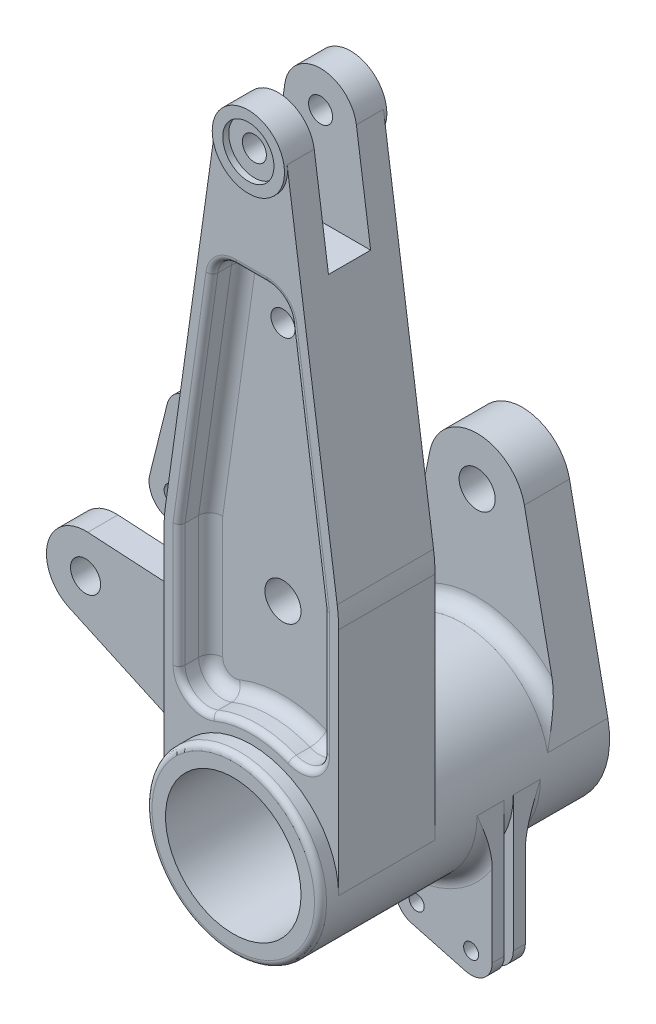
SolidWorks part; units mm, degrees
ref_plane "Front Plane" through (0, 0, 0) normal (0, 0, 1) x (1, 0, 0)
ref_plane "Top Plane" through (0, 0, 0) normal (0, 1, 0) x (1, 0, 0)
ref_plane "Right Plane" through (0, 0, 0) normal (1, 0, 0) x (0, 0, -1)
sketch "Sketch1" plane through (0, 0, 0) normal (0, 0, 1) x (1, 0, 0)
  circle A0 centre (0, 0) radius 22.5
  circle A1 centre (0, 0) radius 29
  dimension "D1" = 45
  dimension "D2" = 6.5
extrude "Boss-Extrude1" add sketch "Sketch1" along normal blind 96
sketch "Sketch2" plane through (0, 0, 0) normal (0, 0, -1) x (-1, 0, 0)
  line L0 (0, 0) -> (0, 65) construction
  line L1 (-28.4141, 5.8) -> (-15.6767, 68.2)
  line L2 (15.6769, 68.1992) -> (22.86, 33)
  line L3 (22.86, 33) -> (101.2121, 44.9958)
  line L4 (101.2121, 44.9958) -> (110.5, 7.633)
  line L5 (110.5, 7.633) -> (9.5035, -27.3986)
  line L6 (0, 0) -> (105.856, 26.3144) construction
  arc A0 (-15.6767, 68.2) -> (15.6769, 68.1992) centre (0, 65) cw
  circle A1 centre (0, 0) radius 29
  circle A2 centre (0, 0) radius 29
  circle M7 centre (0, 0) radius 29
  dimension "D2" = 16
  dimension "D1" = 0
  dimension "D3" = 65
  dimension "D4" = 33
  dimension "D5" = 110.5
  dimension "D6" = 38.5
  dimension "D7" = 76.04
  dimension "D8" = 22.86
extrude "Boss-Extrude2" add sketch "Sketch2" against normal blind 15 contours A0 L1 L5 L4 L3 L2 M7 region at (-41.2413, 26.7949, 0)
fillet "Fillet1" radius 8 2 edges at (-101.2121, 44.9958, 7.5) (-110.5, 7.633, 7.5)
fillet "Fillet2" radius 20 1 edges at (-22.86, 33, 7.5)
sketch "Sketch3" plane through (0, 0, 15) normal (0, 0, 1) x (1, 0, 0)
  line L0 (-105.8547, 26.3197) -> (-62.2845, 15.4888) construction
  line L2 (-58.6658, 30.0457) -> (-65.9031, 0.9318) construction
  line L5 (-15.6769, 68.1992) -> (-19.0538, 51.6515)
  line L6 (-41.6767, 35.8809) -> (-93.9982, 43.8914)
  line L7 (-102.9727, 37.9135) -> (-108.7368, 14.726)
  line L8 (-103.5947, 5.2378) -> (-9.5035, -27.3986)
  line L9 (28.4141, 5.8) -> (15.6767, 68.2)
  line L10 (-15.6769, 68.1992) -> (-19.0538, 51.6515)
  line L11 (-41.6767, 35.8809) -> (-93.9982, 43.8914)
  line L12 (-102.9727, 37.9135) -> (-108.7368, 14.726)
  line L13 (-103.5947, 5.2378) -> (-9.5035, -27.3986)
  line L14 (28.4141, 5.8) -> (15.6767, 68.2)
  circle A0 centre (-95.209, 35.9835) radius 3
  circle A1 centre (-100.9731, 12.796) radius 3
  circle A2 centre (0, 65) radius 6
  circle A3 centre (-58.6658, 30.0457) radius 3
  circle A4 centre (-65.9031, 0.9318) radius 3
  arc A5 (-41.6767, 35.8809) -> (-19.0538, 51.6515) centre (-38.6499, 55.6505) ccw
  arc A6 (-93.9982, 43.8914) -> (-102.9727, 37.9135) centre (-95.209, 35.9835) ccw
  arc A7 (-108.7368, 14.726) -> (-103.5947, 5.2378) centre (-100.9731, 12.796) ccw
  arc A8 (28.4141, 5.8) -> (-9.5035, -27.3986) centre (0, 0) ccw
  arc A9 (15.6767, 68.2) -> (-15.6769, 68.1992) centre (0, 65) ccw
  arc A10 (-41.6767, 35.8809) -> (-19.0538, 51.6515) centre (-38.6499, 55.6505) ccw
  arc A11 (-93.9982, 43.8914) -> (-102.9727, 37.9135) centre (-95.209, 35.9835) ccw
  arc A12 (-108.7368, 14.726) -> (-103.5947, 5.2378) centre (-100.9731, 12.796) ccw
  arc A13 (28.4141, 5.8) -> (-9.5035, -27.3986) centre (0, 0) ccw
  arc A14 (15.6767, 68.2) -> (-15.6769, 68.1992) centre (0, 65) ccw
  circle A15 centre (-84.0696, 20.9042) radius 5
  point P23 (-62.2845, 15.4888)
  dimension "D2" = 10
  dimension "D3" = 6
  dimension "D4" = 12
  dimension "D5" = 30
  dimension "D6" = 45
  dimension "D1" = 0
extrude "Cut-Extrude1" cut sketch "Sketch3" against normal blind 15 contours A0 | A1 | A3 | A4 | A2 | A15
sketch "Sketch7" plane through (0, 0, 15) normal (0, 0, 1) x (1, 0, 0)
  line L0 (-41.6767, 35.8809) -> (-53.6045, -12.1018)
  line L3 (-65.9031, 0.9318) -> (-100.9731, 12.796) construction
  line L5 (-15.6769, 68.1992) -> (-19.0538, 51.6515)
  line L6 (-41.6767, 35.8809) -> (-93.9982, 43.8914)
  line L7 (-102.9727, 37.9135) -> (-108.7368, 14.726)
  line L8 (-103.5947, 5.2378) -> (-9.5035, -27.3986)
  line L9 (28.4141, 5.8) -> (15.6767, 68.2)
  line L10 (-15.6769, 68.1992) -> (-19.0538, 51.6515)
  line L11 (-41.6767, 35.8809) -> (-93.9982, 43.8914)
  line L12 (-102.9727, 37.9135) -> (-108.7368, 14.726)
  line L13 (-103.5947, 5.2378) -> (-9.5035, -27.3986)
  line L14 (28.4141, 5.8) -> (15.6767, 68.2)
  arc A5 (-41.6767, 35.8809) -> (-19.0538, 51.6515) centre (-38.6499, 55.6505) ccw
  arc A6 (-93.9982, 43.8914) -> (-102.9727, 37.9135) centre (-95.209, 35.9835) ccw
  arc A7 (-108.7368, 14.726) -> (-103.5947, 5.2378) centre (-100.9731, 12.796) ccw
  arc A8 (28.4141, 5.8) -> (-9.5035, -27.3986) centre (0, 0) ccw
  arc A9 (15.6767, 68.2) -> (-15.6769, 68.1992) centre (0, 65) ccw
  arc A10 (-41.6767, 35.8809) -> (-19.0538, 51.6515) centre (-38.6499, 55.6505) ccw
  arc A11 (-93.9982, 43.8914) -> (-102.9727, 37.9135) centre (-95.209, 35.9835) ccw
  arc A12 (-108.7368, 14.726) -> (-103.5947, 5.2378) centre (-100.9731, 12.796) ccw
  arc A13 (28.4141, 5.8) -> (-9.5035, -27.3986) centre (0, 0) ccw
  arc A14 (15.6767, 68.2) -> (-15.6769, 68.1992) centre (0, 65) ccw
  circle M13 centre (-100.9731, 12.796) radius 3
  circle M14 centre (-58.6658, 30.0457) radius 3
  circle M15 centre (-65.9031, 0.9318) radius 3
  circle M17 centre (-95.209, 35.9835) radius 3
  line M20 (-41.6767, 35.8809) -> (-93.9982, 43.8914)
  arc M21 (-93.9982, 43.8914) -> (-102.9727, 37.9135) centre (-95.209, 35.9835) ccw
  line M22 (-102.9727, 37.9135) -> (-108.7368, 14.726)
  arc M23 (-108.7368, 14.726) -> (-103.5947, 5.2378) centre (-100.9731, 12.796) ccw
  line M24 (-103.5947, 5.2378) -> (-9.5035, -27.3986)
  dimension "D1" = 0
extrude "Cut-Extrude3" cut sketch "Sketch7" against normal mid plane 5 from offset 7.5 contours L0 M20 M21 M22 M23 M24 M14 M17 M15 M13 region at (-75.0763, 18.6886, 15) offset against normal yes
ref_plane "Plane1" through (0, 0, 74) normal (0, 0, 1) x (1, 0, 0)
sketch "Sketch8" plane through (0, 0, 74) normal (0, 0, 1) x (1, 0, 0)
  line L0 (-29, 0) -> (-29, 80)
  line L1 (-29, 80) -> (-11.883, 201.6717)
  line L2 (11.883, 201.6717) -> (29, 80)
  line L3 (29, 80) -> (29, 0)
  line L4 (0, 0) -> (0, 200) construction
  line L5 (0, 0) -> (0, 200) construction
  circle A0 centre (0, 0) radius 29 construction
  circle A1 centre (0, 0) radius 29
  arc A2 (-11.883, 201.6717) -> (11.883, 201.6717) centre (0, 200) cw
  circle A3 centre (0, 200) radius 12
  circle A4 centre (0, 200) radius 4
  circle A5 centre (0, 200) radius 8.5
  dimension "D3" = 12
  dimension "D4" = 8
  dimension "D5" = 17
  dimension "D1" = 200
  dimension "D2" = 80
extrude "Boss-Extrude3" add sketch "Sketch8" along normal mid plane 32 contours A3 L1 L0 A1 L3 L2 | A2 A3 A5 | A5 A4 | A4 region at (0, 96.6166, 74) region at (0, 211.6606, 74) region at (0, 200, 74) region at (-8.2596, 200, 74)
sketch "Sketch9" plane through (0, 0, 90) normal (0, 0, 1) x (1, 0, 0)
  line L0 (-12.1335, 164) -> (-24, 79.65)
  line L1 (-24, 79.65) -> (-24, 24.0832)
  line L2 (24, 24.0832) -> (24, 79.65)
  line L3 (24, 79.65) -> (12.1335, 164)
  line L4 (29, 80) -> (11.883, 201.6717)
  line L5 (-11.883, 201.6717) -> (-29, 80)
  line L6 (-29, 80) -> (-29, 0)
  line L7 (29, 0) -> (29, 80)
  line L8 (29, 80) -> (11.883, 201.6717)
  line L9 (-11.883, 201.6717) -> (-29, 80)
  line L10 (-29, 80) -> (-29, 0)
  line L11 (29, 0) -> (29, 80)
  line L12 (-12.1335, 164) -> (12.1335, 164)
  line L13 (24, 79.65) -> (6.9317, 200.9752) construction
  line L14 (-6.9317, 200.9752) -> (-24, 79.65) construction
  arc A2 (11.883, 201.6717) -> (-11.883, 201.6717) centre (0, 200) ccw
  arc A3 (29, 0) -> (-29, 0) centre (0, 0) ccw
  arc A4 (11.883, 201.6717) -> (-11.883, 201.6717) centre (0, 200) ccw
  arc A5 (29, 0) -> (-29, 0) centre (0, 0) ccw
  arc A7 (24, 24.0832) -> (-24, 24.0832) centre (0, 0) ccw
  arc A9 (6.9317, 200.9752) -> (-6.9317, 200.9752) centre (0, 200) ccw construction
  dimension "D5" = 36
  dimension "D1" = 0
  dimension "D4" = 5
extrude "Cut-Extrude4" cut sketch "Sketch9" against normal blind 10.5 contours A7 L2 L3 L12 L0 L1 region at (0, 90.281, 90)
fillet "Fillet3" radius 8 4 edges at (-24, 24.0832, 84.75) (24, 24.0832, 84.75) (-12.1335, 164, 84.75) (12.1335, 164, 84.75)
fillet "Fillet4" radius 50 2 edges at (29, 80, 74) (-29, 80, 74)
fillet "Fillet5" radius 4 10 edges at (-20.4508, 32.1854, 79.5) (0, 34, 79.5) (20.4508, 32.1854, 79.5) (24, 59.2415, 79.5) (-24, 59.2415, 79.5) (18.5511, 118.3822, 79.5) (10.4282, 162.038, 79.5) (-18.5511, 118.3822, 79.5) (-10.4282, 162.038, 79.5) (0, 164, 79.5)
sketch "Sketch10" plane through (0, 0, 58) normal (0, 0, -1) x (-1, 0, 0)
  line L0 (-12.1335, 164) -> (-23.8101, 81)
  line L3 (23.5612, 82.7691) -> (12.1335, 164)
  line L4 (-11.883, 201.6717) -> (-28.5124, 83.4657)
  line L5 (-29, 76.5002) -> (-29, 0)
  line L6 (29, 0) -> (29, 76.5002)
  line L7 (28.5124, 83.4657) -> (11.883, 201.6717)
  line L8 (-11.883, 201.6717) -> (-28.5124, 83.4657)
  line L9 (-29, 76.5002) -> (-29, 0)
  line L10 (29, 0) -> (29, 76.5002)
  line L11 (28.5124, 83.4657) -> (11.883, 201.6717)
  line L13 (-12.1335, 164) -> (12.1335, 164)
  line L14 (-23.8101, 81) -> (23.7745, 81)
  line L15 (-24, 76.5002) -> (-24, 24.0832) construction
  line L16 (24, 24.0832) -> (24, 76.5002) construction
  line L18 (-6.9317, 200.9752) -> (-23.5612, 82.7691) construction
  line L19 (23.5612, 82.7691) -> (6.9317, 200.9752) construction
  arc A2 (23.7745, 81) -> (23.5612, 82.7691) centre (-21, 76.5002) ccw
  arc A4 (-28.5124, 83.4657) -> (-29, 76.5002) centre (21, 76.5002) ccw
  arc A5 (29, 0) -> (-29, 0) centre (0, 0) ccw
  arc A6 (29, 76.5002) -> (28.5124, 83.4657) centre (-21, 76.5002) ccw
  arc A7 (11.883, 201.6717) -> (-11.883, 201.6717) centre (0, 200) ccw
  arc A8 (-28.5124, 83.4657) -> (-29, 76.5002) centre (21, 76.5002) ccw
  arc A9 (29, 0) -> (-29, 0) centre (0, 0) ccw
  arc A10 (29, 76.5002) -> (28.5124, 83.4657) centre (-21, 76.5002) ccw
  arc A11 (11.883, 201.6717) -> (-11.883, 201.6717) centre (0, 200) ccw
  arc A12 (24, 24.0832) -> (-24, 24.0832) centre (0, 0) ccw construction
  arc A13 (-23.5612, 82.7691) -> (-24, 76.5002) centre (21, 76.5002) ccw construction
  arc A15 (24, 76.5002) -> (23.5612, 82.7691) centre (-21, 76.5002) ccw construction
  arc A16 (6.9317, 200.9752) -> (-6.9317, 200.9752) centre (0, 200) ccw construction
  point P28 (0, 29)
  dimension "D4" = 52
  dimension "D3" = 36
  dimension "D1" = 0
  dimension "D2" = 5
extrude "Cut-Extrude5" cut sketch "Sketch10" against normal blind 10.5 contours L3 L13 L0 L14 A2
fillet "Fillet6" radius 8 4 edges at (-23.7745, 81, 63.25) (-12.1335, 164, 63.25) (12.1335, 164, 63.25) (23.8101, 81, 63.25)
fillet "Fillet7" radius 4 8 edges at (-20.6439, 83.7519, 68.5) (-17.815, 123.6145, 68.5) (-10.4282, 162.038, 68.5) (0, 81, 68.5) (20.6439, 83.7519, 68.5) (17.815, 123.6145, 68.5) (10.4282, 162.038, 68.5) (0, 164, 68.5)
sketch "Sketch13" plane through (0, 0, 74) normal (0, 0, 1) x (1, 0, 0)
  line L0 (-16.62, 168) -> (16.62, 168)
  line L4 (29, 0) -> (29, 76.5002)
  line L5 (28.5124, 83.4657) -> (11.883, 201.6717)
  line L6 (-11.883, 201.6717) -> (-28.5124, 83.4657)
  line L7 (-29, 76.5002) -> (-29, 0)
  line L8 (29, 0) -> (29, 76.5002)
  line L9 (16.62, 168) -> (11.883, 201.6717)
  line L10 (-11.883, 201.6717) -> (-16.62, 168)
  line L11 (-29, 76.5002) -> (-29, 0)
  arc A4 (29, 76.5002) -> (28.5124, 83.4657) centre (-21, 76.5002) ccw
  arc A5 (11.883, 201.6717) -> (-11.883, 201.6717) centre (0, 200) ccw
  arc A6 (-28.5124, 83.4657) -> (-29, 76.5002) centre (21, 76.5002) ccw
  arc A7 (29, 0) -> (-29, 0) centre (0, 0) ccw
  arc A8 (29, 76.5002) -> (28.5124, 83.4657) centre (-21, 76.5002) ccw
  arc A9 (11.883, 201.6717) -> (-11.883, 201.6717) centre (0, 200) ccw
  arc A10 (-28.5124, 83.4657) -> (-29, 76.5002) centre (21, 76.5002) ccw
  arc A11 (29, 0) -> (-29, 0) centre (0, 0) ccw
  dimension "D2" = 32
  dimension "D1" = 0
extrude "Cut-Extrude7" cut sketch "Sketch13" against normal mid plane 14 contours L9 A9 L10 L0
sketch "Sketch11" plane through (0, 0, 58) normal (0, 0, -1) x (-1, 0, 0)
  line L4 (-11.883, 201.6717) -> (-28.5124, 83.4657)
  line L5 (-29, 76.5002) -> (-29, 0)
  line L6 (29, 0) -> (29, 76.5002)
  line L7 (28.5124, 83.4657) -> (11.883, 201.6717)
  line L8 (-11.883, 201.6717) -> (-28.5124, 83.4657)
  line L9 (-29, 76.5002) -> (-29, 0)
  line L10 (29, 0) -> (29, 76.5002)
  line L11 (28.5124, 83.4657) -> (11.883, 201.6717)
  circle A0 centre (0, 200) radius 12
  arc A4 (-28.5124, 83.4657) -> (-29, 76.5002) centre (21, 76.5002) ccw
  arc A5 (29, 0) -> (-29, 0) centre (0, 0) ccw
  arc A6 (29, 76.5002) -> (28.5124, 83.4657) centre (-21, 76.5002) ccw
  arc A7 (11.883, 201.6717) -> (-11.883, 201.6717) centre (0, 200) ccw
  arc A8 (-28.5124, 83.4657) -> (-29, 76.5002) centre (21, 76.5002) ccw
  arc A9 (29, 0) -> (-29, 0) centre (0, 0) ccw
  arc A10 (29, 76.5002) -> (28.5124, 83.4657) centre (-21, 76.5002) ccw
  arc A11 (11.883, 201.6717) -> (-11.883, 201.6717) centre (0, 200) ccw
  arc M25 (11.883, 201.6717) -> (-11.883, 201.6717) centre (0, 200) ccw
  dimension "D1" = 0
extrude "Boss-Extrude4" add sketch "Sketch11" along normal mid plane 2 contours A0 M25 region at (0, 200, 58)
sketch "Sketch16" plane through (0, 0, 57) normal (0, 0, -1) x (-1, 0, 0)
  point P0 (0, 200)
hole_wizard "Hole1" positions "Sketch16" profile "Sketch15" legacy end condition up to next
sketch "Sketch15" plane through (0, 200, 57) normal (1, 0, 0) x (0, 1, 0)
  line L0 (0, 0) -> (0, 10)
  line L1 (0, 10) -> (4, 10)
  line L2 (4, 10) -> (4, 2)
  line L3 (4, 2) -> (8.5, 2)
  line L4 (8.5, 2) -> (8.5, 0)
  line L5 (8.5, 0) -> (0, 0)
  line L6 (0, 110) -> (0, -10) construction
  dimension "Diameter" = 8
  dimension "Depth" = 10
  dimension "C-Bore Diameter" = 17
  dimension "C-Bore Depth" = 2
mirror "Mirror2" about plane through (0, 0, 74) normal (0, 0, 1) of "Hole1", "Boss-Extrude4"
fillet "Fillet8" radius 2 10 edges at (-24, 59.2415, 90) (-20.4508, 32.1854, 90) (0, 34, 90) (20.4508, 32.1854, 90) (-18.5511, 118.3822, 90) (-10.4282, 162.038, 90) (18.5511, 118.3822, 90) (10.4282, 162.038, 90) (24, 59.2415, 90) (0, 164, 90)
fillet "Fillet9" radius 2 8 edges at (-20.6439, 83.7519, 58) (-17.815, 123.6145, 58) (-10.4282, 162.038, 58) (0, 81, 58) (20.6439, 83.7519, 58) (17.815, 123.6145, 58) (10.4282, 162.038, 58) (0, 164, 58)
sketch "Sketch17" plane through (0, 0, 79.5) normal (0, 0, 1) x (1, 0, 0)
  line L0 (0, 200) -> (0, 0) construction
  circle A0 centre (0, 65) radius 6
  circle A1 centre (0, 145) radius 4
  point P4 (0, 100)
  point P7 (0, 0)
  point P8 (0, 0)
  dimension "D2" = 12
  dimension "D4" = 8
  dimension "D1" = 100
  dimension "D3" = 35
  dimension "D5" = 45
extrude "Cut-Extrude8" cut sketch "Sketch17" against normal blind 25
ref_plane "Plane2" through (0, 0, 51) normal (0, 0, -1) x (-1, 0, 0)
sketch "Sketch19" plane through (0, 0, 51) normal (0, 0, -1) x (-1, 0, 0)
  line L0 (-1.6796, 28.9513) -> (83.3167, 33.8824)
  line L1 (89.4827, 9.0848) -> (12.0753, -26.3664)
  circle A0 centre (0, 0) radius 29 construction
  circle A1 centre (0, 0) radius 29
  circle A2 centre (84.0696, 20.9042) radius 5 construction
  circle A3 centre (84.0696, 20.9042) radius 5
  arc A4 (83.3167, 33.8824) -> (89.4827, 9.0848) centre (84.0696, 20.9042) cw
  dimension "D1" = 13
extrude "Boss-Extrude5" add sketch "Sketch19" against normal blind 15 contours A4 L0 A1 L1 A3 region at (-53.4735, 13.2964, 51)
sketch "Sketch20" plane through (1.6796, 28.9513, 0) normal (0.0579, 0.9983, 0) x (0.9983, -0.0579, 0)
  line L0 (-85.1392, -61) -> (-42.1392, -61)
  line L1 (-42.1392, -61) -> (-30.7312, -66)
  line L6 (-30.7312, -66) -> (-30.7312, -58)
  line L7 (-30.7312, -58) -> (0, -58)
  line L8 (0, -58) -> (0, -51)
  line L9 (0, -51) -> (-85.1392, -51)
  line L10 (-85.1392, -51) -> (-85.1392, -66)
  line L11 (-85.1392, -66) -> (-30.7312, -66)
  line L12 (-30.7312, -66) -> (-30.7312, -58)
  line L13 (-30.7312, -58) -> (0, -58)
  line L14 (0, -58) -> (0, -51)
  line L15 (0, -51) -> (-85.1392, -51)
  line L16 (-85.1392, -51) -> (-85.1392, -66)
  line L17 (-85.1392, -66) -> (-30.7312, -66)
  line L22 (-98.1392, -66) -> (-85.1392, -66) construction
  line L23 (-98.1392, -66) -> (-85.1392, -66)
  line L24 (-85.1392, -61) -> (-98.1392, -61)
  line L25 (-98.1392, -61) -> (-98.1392, -66)
  line M12 (-85.1392, -51) -> (-85.1392, -66)
  line M13 (-85.1392, -66) -> (-30.7312, -66)
  dimension "D2" = 43
  dimension "D3" = 5
  dimension "D1" = 0
extrude "Cut-Extrude9" cut sketch "Sketch20" against normal blind 77 contours L1 L0 M12 M13 | L24 L25 L23 M12 region at (-58.8944, 32.4655, 63.5976) region at (-89.8057, 34.2589, 63.5)
fillet "Fillet10" radius 5 1 edges at (-29, 30.7312, 62)
ref_plane "Plane3" through (0, 0, 28) normal (0, 0, -1) x (-1, 0, 0)
sketch "Sketch21" plane through (0, 0, 28) normal (0, 0, -1) x (-1, 0, 0)
  line L0 (-29, 76.5002) -> (-29, 0) construction
  line L1 (-29, 76.5002) -> (-29, 0)
  line L2 (103.5947, 5.2378) -> (9.5035, -27.3986) construction
  line L3 (103.5947, 5.2378) -> (9.5035, -27.3986)
  line L4 (-29, 0) -> (-29, -44.8433)
  line L5 (-20.1883, -51.6048) -> (-2.1127, -46.7615)
  line L6 (-69.4692, 0) -> (76.3813, 0) construction
  line L12 (108.7368, 14.726) -> (102.9727, 37.9135)
  line L13 (93.9982, 43.8914) -> (41.6767, 35.8809)
  line L14 (19.0538, 51.6515) -> (15.6769, 68.1992)
  line L15 (-15.6767, 68.2) -> (-28.4141, 5.8)
  line L16 (9.5035, -27.3986) -> (103.5947, 5.2378)
  line L17 (108.7368, 14.726) -> (102.9727, 37.9135)
  line L18 (93.9982, 43.8914) -> (41.6767, 35.8809)
  line L19 (19.0538, 51.6515) -> (15.6769, 68.1992)
  line L20 (-15.6767, 68.2) -> (-28.4141, 5.8)
  line L21 (9.5035, -27.3986) -> (103.5947, 5.2378)
  arc A0 (-29, -44.8433) -> (-20.1883, -51.6048) centre (-22, -44.8433) ccw
  arc A1 (9.5035, -27.3986) -> (2.9541, -38.7015) centre (12.7805, -36.8464) ccw
  arc A2 (2.9541, -38.7015) -> (-2.1127, -46.7615) centre (-3.9244, -40) cw
  circle A3 centre (-22, -44.8433) radius 2.5
  circle A4 centre (-3.9244, -40) radius 2.5
  arc A10 (102.9727, 37.9135) -> (93.9982, 43.8914) centre (95.209, 35.9835) ccw
  arc A11 (19.0538, 51.6515) -> (41.6767, 35.8809) centre (38.6499, 55.6505) ccw
  arc A12 (15.6769, 68.1992) -> (-15.6767, 68.2) centre (0, 65) ccw
  arc A13 (-28.4141, 5.8) -> (9.5035, -27.3986) centre (0, 0) ccw
  arc A14 (103.5947, 5.2378) -> (108.7368, 14.726) centre (100.9731, 12.796) ccw
  arc A15 (102.9727, 37.9135) -> (93.9982, 43.8914) centre (95.209, 35.9835) ccw
  arc A16 (19.0538, 51.6515) -> (41.6767, 35.8809) centre (38.6499, 55.6505) ccw
  arc A17 (15.6769, 68.1992) -> (-15.6767, 68.2) centre (0, 65) ccw
  arc A18 (-28.4141, 5.8) -> (9.5035, -27.3986) centre (0, 0) ccw
  arc A19 (103.5947, 5.2378) -> (108.7368, 14.726) centre (100.9731, 12.796) ccw
  dimension "D2" = 7
  dimension "D3" = 10
  dimension "D4" = 7
  dimension "D6" = 5
  dimension "D7" = 5
  dimension "D1" = 15
  dimension "D5" = 40
  dimension "D8" = 0
extrude "Boss-Extrude6" add sketch "Sketch21" against normal blind 11 contours A18 L4 A0 L5 A2 A1 A4 A3 region at (15.662, -35.0234, 28)
sketch "Sketch24" plane through (0, 0, 28) normal (0, 0, -1) x (-1, 0, 0)
  line L2 (-29, 0) -> (-29, -44.8433)
  line L3 (-20.1883, -51.6048) -> (-2.1127, -46.7615)
  line L4 (-29, 0) -> (-29, -44.8433)
  line L5 (-20.1883, -51.6048) -> (-2.1127, -46.7615)
  arc A4 (-29, 0) -> (9.5035, -27.3986) centre (0, 0) ccw
  arc A5 (-29, -44.8433) -> (-20.1883, -51.6048) centre (-22, -44.8433) ccw
  arc A6 (-2.1127, -46.7615) -> (2.9541, -38.7015) centre (-3.9244, -40) ccw
  arc A7 (9.5035, -27.3986) -> (2.9541, -38.7015) centre (12.7805, -36.8464) ccw
  arc A8 (-29, 0) -> (9.5035, -27.3986) centre (0, 0) ccw
  arc A9 (-29, -44.8433) -> (-20.1883, -51.6048) centre (-22, -44.8433) ccw
  arc A10 (-2.1127, -46.7615) -> (2.9541, -38.7015) centre (-3.9244, -40) ccw
  arc A11 (9.5035, -27.3986) -> (2.9541, -38.7015) centre (12.7805, -36.8464) ccw
  dimension "D1" = 0
extrude "Cut-Extrude10" cut sketch "Sketch24" against normal mid plane 3 from offset 5.5 offset against normal yes
fillet "Fillet11" radius 5 2 edges at (16.8137, -23.6284, 39) (16.8137, -23.6284, 28)
ref_plane "Plane4" through (0, 0, 74) normal (0, 0, 1) x (1, 0, 0)
fillet "Fillet12" radius 5 2 edges at (-28.143, 6.9979, 51) (-19.1034, 21.8188, 15)
fillet "Fillet13" radius 2 1 edges at (29, 0, 96)
